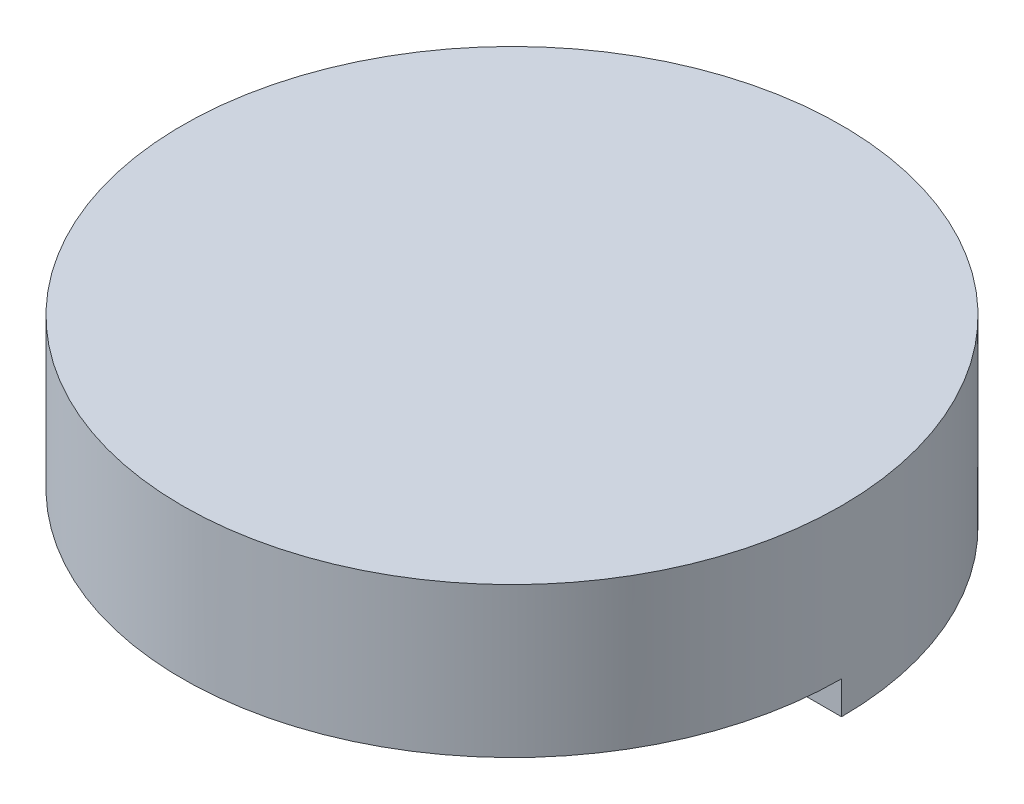
SolidWorks part; units mm, degrees
ref_plane "Front Plane" through (0, 0, 0) normal (0, 0, 1) x (1, 0, 0)
ref_plane "Top Plane" through (0, 0, 0) normal (0, 1, 0) x (1, 0, 0)
ref_plane "Right Plane" through (0, 0, 0) normal (1, 0, 0) x (0, 0, -1)
sketch "Sketch2" plane through (0, 0, 0) normal (0, 1, 0) x (1, 0, 0)
  circle A0 centre (0, 0) radius 11
  dimension "D1" = 22
extrude "Boss-Extrude1" add sketch "Sketch2" along normal blind 5
sketch "Sketch3" plane through (0, 0, 0) normal (0, 1, 0) x (1, 0, 0)
  line L0 (-10, 0) -> (-11, 0)
  line L1 (10, 0) -> (11, 0)
  arc A0 (-11, 0) -> (11, 0) centre (0, 0) cw
  circle A1 centre (0, 0) radius 11 construction
  arc A3 (-10, 0) -> (10, 0) centre (0, 0) cw
  dimension "D1" = 1
extrude "Boss-Extrude2" add sketch "Sketch3" against normal blind 0.6
sketch "Sketch4" plane through (0, -0.6, 0) normal (0, -1, 0) x (1, 0, 0)
  line L0 (-11, 0) -> (-8.5, 0)
  line L1 (8.5, 0) -> (11, 0)
  arc A0 (-11, 0) -> (11, 0) centre (0, 0) ccw
  arc A2 (-8.5, 0) -> (8.5, 0) centre (0, 0) ccw
  dimension "D1" = 2.5
extrude "Boss-Extrude3" add sketch "Sketch4" along normal blind 0.5
